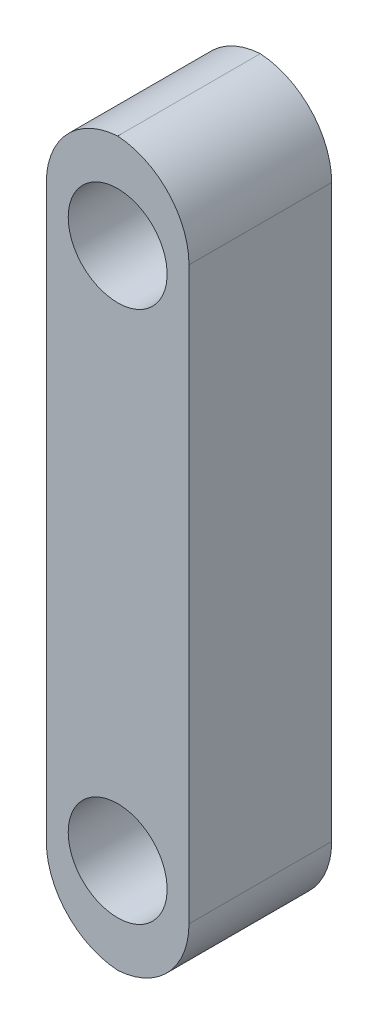
SolidWorks part; units mm, degrees
ref_plane "Front Plane" through (0, 0, 0) normal (0, 0, 1) x (1, 0, 0)
ref_plane "Top Plane" through (0, 0, 0) normal (0, 1, 0) x (1, 0, 0)
ref_plane "Right Plane" through (0, 0, 0) normal (1, 0, 0) x (0, 0, -1)
sketch "Sketch1" plane through (0, 0, 0) normal (0, 0, 1) x (1, 0, 0)
  line L1 (-4.7625, 24.13) -> (4.7625, 24.13)
  line L2 (-4.7625, 24.13) -> (-4.7625, -24.13)
  line L3 (-4.7625, -24.13) -> (4.7625, -24.13)
  line L4 (4.7625, 24.13) -> (4.7625, -24.13)
  line L5 (-4.7625, 24.13) -> (4.7625, -24.13) construction
  line L6 (-4.7625, -24.13) -> (4.7625, 24.13) construction
  circle A0 centre (0, -17.78) radius 3.302
  circle A1 centre (0, 17.78) radius 3.302
  point P0 (0, 0)
  dimension "D3" = 6.604
  dimension "D1" = 48.26
  dimension "D2" = 9.525
  dimension "D4" = 6.35
  dimension "D5" = 6.35
extrude "Boss-Extrude1" add sketch "Sketch1" along normal blind 9.525
fillet "Fillet1" radius 5.08 4 edges at (-4.7625, -24.13, 4.7625) (4.7625, -24.13, 4.7625) (4.7625, 24.13, 4.7625) (-4.7625, 24.13, 4.7625)
